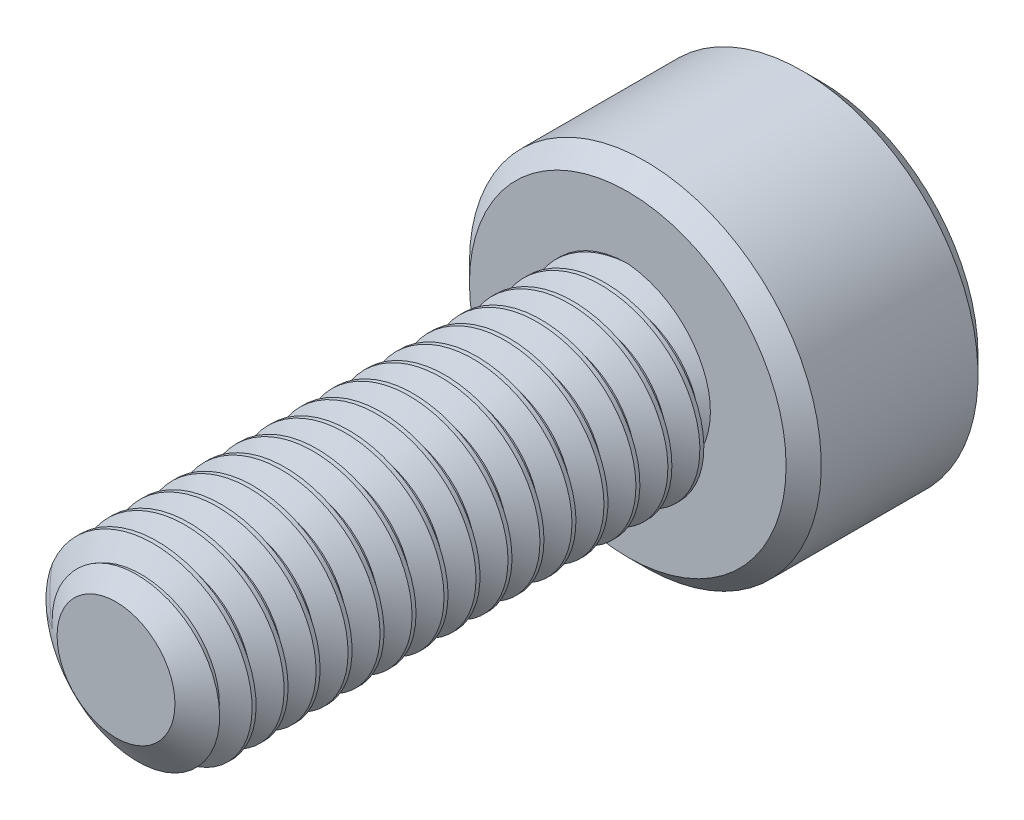
SolidWorks part; units mm, degrees
ref_plane "Front Plane" through (0, 0, 0) normal (0, 0, 1) x (1, 0, 0)
ref_plane "Top Plane" through (0, 0, 0) normal (0, 1, 0) x (1, 0, 0)
ref_plane "Right Plane" through (0, 0, 0) normal (1, 0, 0) x (0, 0, -1)
sketch "Sketch1" plane through (0, 0, 0) normal (0, 0, 1) x (1, 0, 0)
  circle A0 centre (0, 0) radius 1.5
  dimension "OD" = 3
extrude "Extrude1" add sketch "Sketch1" against normal blind 8
sketch "Sketch2" plane through (0, 0, 0) normal (0, 0, 1) x (1, 0, 0)
  circle A0 centre (0, 0) radius 1.5 construction
  circle A1 centre (0, 0) radius 1.5
curve "Helix/Spiral1" pitch 0.5 height 8.5 radius 1.5 centre (0, 0, 0) axis (0, 0, -1) start towards (0, 1, 0) parameters "pitch"=0.5
sketch "Sketch3" plane through (0, 0, 0) normal (1, 0, 0) x (0, 0, -1)
  line L0 (-0.4375, 1.5) -> (-0.25, 1.1752)
  line L1 (-0.25, 1.1752) -> (-0.1875, 1.1752)
  line L2 (-0.1875, 1.1752) -> (0, 1.5)
  line L3 (-0.4375, 1.5) -> (0, 1.5)
  line L4 (-0.2188, 1.5) -> (-0.2188, 1.1752) construction
  line L5 (-0.3438, 1.3376) -> (-0.0938, 1.3376) construction
  line L6 (0, 1.5) -> (0, -1.5) construction
  dimension "D1" = 0.0625
  dimension "D2" = 0.25
  dimension "D3" = 60
sweep "Cut-Sweep1" cut profiles "Sketch3" path "Helix/Spiral1"
sketch "Sketch4" plane through (0, 0, 0) normal (1, 0, 0) x (0, 0, -1)
  line L0 (0.4053, 1.5) -> (0, 0.9212)
  line L1 (0, 0.9212) -> (0, 1.5)
  line L2 (0.4053, 1.5) -> (0, 1.5)
  line L3 (-0.4375, 1.5) -> (0, 1.5) construction
  line L4 (0, 0) -> (7.0209, 0) construction
  dimension "D1" = 55
  dimension "D2" = 0.254
revolve "Cut-Revolve1" cut sketch "Sketch4" angle 360 about L4
sketch "Sketch6" plane through (0, 0, -8) normal (0, 0, -1) x (-1, 0, 0)
  circle A0 centre (0, 0) radius 2.75
  dimension "head dia" = 5.5
extrude "Extrude2" add sketch "Sketch6" along normal blind 3
sketch "Sketch7" plane through (0, 0, -11) normal (0, 0, -1) x (-1, 0, 0)
  line L1 (0, 1.4434) -> (-1.25, 0.7217)
  line L2 (-1.25, 0.7217) -> (-1.25, -0.7217)
  line L3 (-1.25, -0.7217) -> (0, -1.4434)
  line L4 (0, -1.4434) -> (1.25, -0.7217)
  line L5 (1.25, -0.7217) -> (1.25, 0.7217)
  line L6 (1.25, 0.7217) -> (0, 1.4434)
  circle A0 centre (0, 0) radius 1.25 construction
  dimension "hex dia" = 2.5
extrude "Cut-Extrude1" cut sketch "Sketch7" against normal blind 1.875
sketch "Sketch8" plane through (0, 0, -11) normal (0, 0, -1) x (-1, 0, 0)
  circle A0 centre (0, 0) radius 1.4434
extrude "Cut-Extrude2" cut sketch "Sketch8" against normal through all draft 45
chamfer "Chamfer1" distance 0.275 angle 45 2 edges at (-2.75, 0, -11) (-2.75, 0, -8)
sketch "Sketch10" plane through (0, 0, -8) normal (0, 0, 1) x (1, 0, 0)
  circle A1 centre (0, 0) radius 1.5
  circle A2 centre (0, 0) radius 1.5
  dimension "D1" = 0
ref_plane "Plane1" through (0, 0, 0) normal (0, 0, 1) x (1, 0, 0)
extrude "partial thread" [suppressed] add sketch "Sketch10" along normal up to surface (36 mm away) separate body up to plane "Plane1"
chamfer "Chamfer2" [suppressed] distance 0.06 angle 45
combine bodies "Combine1" [suppressed] operation type add bodies to combine 107 108
sketch "Sketch9" plane through (0, 0, 0) normal (1, 0, 0) x (0, 0, -1)
  line L0 (0, 1.5) -> (0, -1.5) construction
  line L1 (1.25, 1.5) -> (1.25, -1.5) construction
  dimension "D1" = 1.25
equation "\"D3@Helix/Spiral1\" = \"screw length@Extrude1\"+\"pitch@Helix/Spiral1\""
equation "\"D1@Sketch3\" = \"pitch@Helix/Spiral1\"*.125"
equation "\"D2@Sketch3\" = \"pitch@Helix/Spiral1\"*.5"
equation "\"D1@Cut-Extrude1\" = \"hex dia@Sketch7\"*.75"
equation "\"D1@Chamfer1\" = \"head dia@Sketch6\"*.05"
equation "\"D1@Sketch9\" = \"pitch@Helix/Spiral1\"*2.5"
equation "\"D1@Chamfer2\"=\"OD@Sketch1\"*.02"
